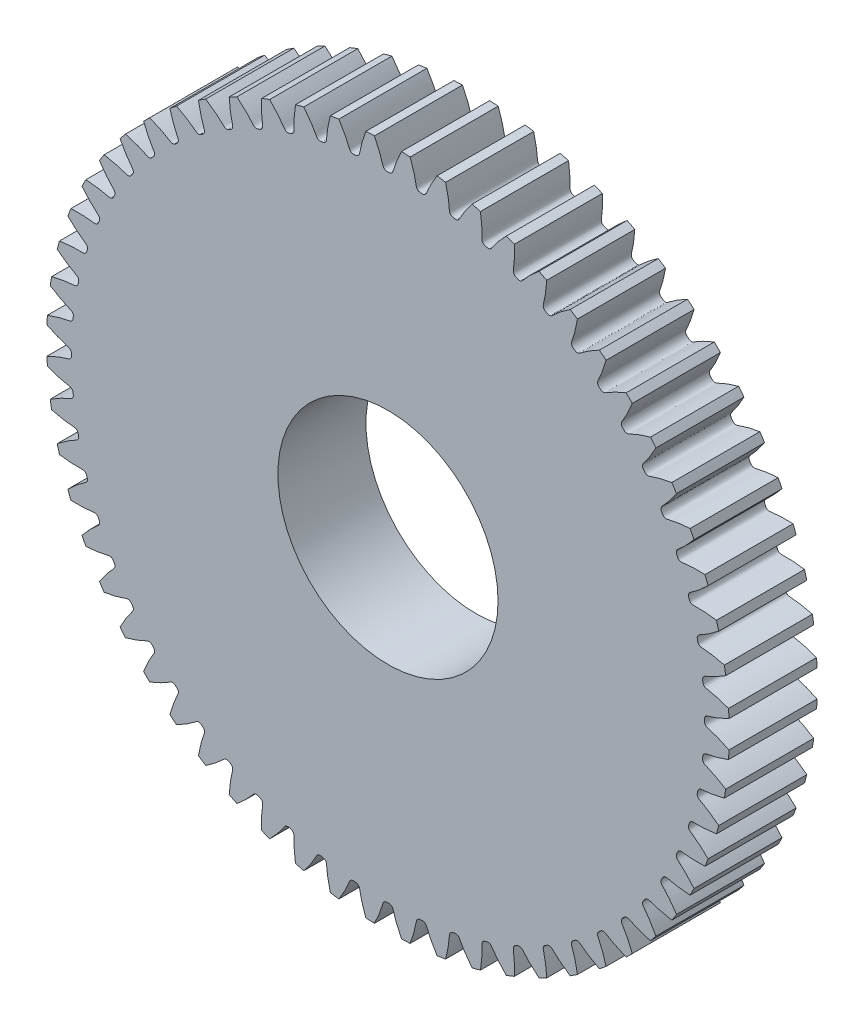
SolidWorks part; units mm, degrees
ref_plane "前视基准面" through (0, 0, 0) normal (0, 0, 1) x (1, 0, 0)
ref_plane "上视基准面" through (0, 0, 0) normal (0, 1, 0) x (1, 0, 0)
ref_plane "右视基准面" through (0, 0, 0) normal (1, 0, 0) x (0, 0, -1)
ref_axis "基准轴1" through (0, 0, 55) along (0, 0, -1)
sketch "SketchRevolveSpurGear2" plane through (0, 0, 0) normal (1, 0, 0) x (0, 0, -1)
  line L0 (0, 0) -> (1, 0) construction
  line L1 (-2, 0) -> (-2, 15.5)
  line L2 (-2, 15.5) -> (2, 15.5)
  line L3 (2, 15.5) -> (2, 0)
  line L4 (2, 0) -> (-2, 0)
revolve "SpurGear2" add sketch "SketchRevolveSpurGear2" angle 360 about L0
sketch "SketchToothSpurGear2" plane through (0, 0, 0) normal (0, 0, 1) x (1, 0, 0)
  arc A0 (15.5123, 0.6275) -> (15.5123, -0.6275) centre (0, 0) cw
  spline S0 degree 3 poles (15.5123, -0.6275) (15.4702, -0.6059) (15.4074, -0.5747) (15.3242, -0.535) (15.2638, -0.507) (15.2047, -0.4804) (15.1469, -0.4552) (15.0904, -0.4313) (15.0354, -0.4087) (14.9817, -0.3874) (14.9294, -0.3673) (14.8785, -0.3484) (14.8291, -0.3307) (14.7812, -0.3141) (14.7348, -0.2986) (14.6898, -0.2841) (14.6464, -0.2708) (14.5851, -0.2522) (14.5304, -0.2395) (14.4856, -0.2201) (14.4657, -0.2095) (14.4444, -0.1952) (14.4216, -0.175) (14.3983, -0.1454) (14.38, -0.1051) (14.373, -0.0545) (14.3761, 0) (14.373, 0.0545) (14.38, 0.1051) (14.3983, 0.1454) (14.4216, 0.175) (14.4444, 0.1952) (14.4657, 0.2095) (14.4856, 0.2201) (14.5304, 0.2395) (14.5851, 0.2522) (14.6464, 0.2708) (14.6898, 0.2841) (14.7348, 0.2986) (14.7812, 0.3141) (14.8291, 0.3307) (14.8785, 0.3484) (14.9294, 0.3673) (14.9817, 0.3874) (15.0354, 0.4087) (15.0904, 0.4313) (15.1469, 0.4552) (15.2047, 0.4804) (15.2638, 0.507) (15.3242, 0.535) (15.4074, 0.5747) (15.4702, 0.6059) (15.5123, 0.6275) knots 0 0 0 0 0.051766 0.076686 0.100963 0.124598 0.147592 0.169943 0.191651 0.212718 0.233143 0.252925 0.272065 0.290563 0.308419 0.325633 0.342204 0.358133 0.395729 0.403327 0.411415 0.420483 0.431261 0.444675 0.461387 0.478965 0.5 0.521035 0.538613 0.555325 0.568739 0.579517 0.588585 0.596673 0.604271 0.641867 0.657796 0.674367 0.691581 0.709437 0.727935 0.747075 0.766857 0.787282 0.808349 0.830057 0.852408 0.875402 0.899037 0.923314 0.948234 1 1 1 1
extrude "ToothExtrudeCutSpurGear2" cut sketch "SketchToothSpurGear2" against normal blind 2 and the other way blind 2
pattern_circular "PatternSpurGear2" count 60 every 6 about axis through (0, 0, 55) along (0, 0, -1) of "ToothExtrudeCutSpurGear2"
sketch "BoreRevolveSketch" plane through (0, 0, 0) normal (1, 0, 0) x (0, 0, -1)
  line L0 (0, 0) -> (1, 0) construction
  line L1 (-2, 0) -> (2, 0)
  line L2 (2, 0) -> (2, 5)
  line L3 (2, 5) -> (-2, 5)
  line L4 (-2, 5) -> (-2, 0)
  dimension "TaperSide1" = 5
  dimension "TaperSide2" = 5
revolve "BoreRevolveCut" cut sketch "BoreRevolveSketch" angle 360 about L0
sketch "AuxiliarySketchSpurGear2" plane through (0, 0, 0) normal (0, 0, 1) x (1, 0, 0)
  circle A0 centre (0, 0) radius 15 construction
  circle A1 centre (0, 0) radius 14.0954 construction
  circle A2 centre (0, 0) radius 14.5457 construction
  circle A3 centre (0, 0) radius 15.5 construction
  circle A4 centre (0, 0) radius 14.375 construction
  dimension "PitchDiameter" = 30
  dimension "BaseDiameter" = 28.1908
  dimension "FormDiameter" = 29.0915
  dimension "MajorDiameter" = 31
  dimension "MinorDiameter" = 28.75
